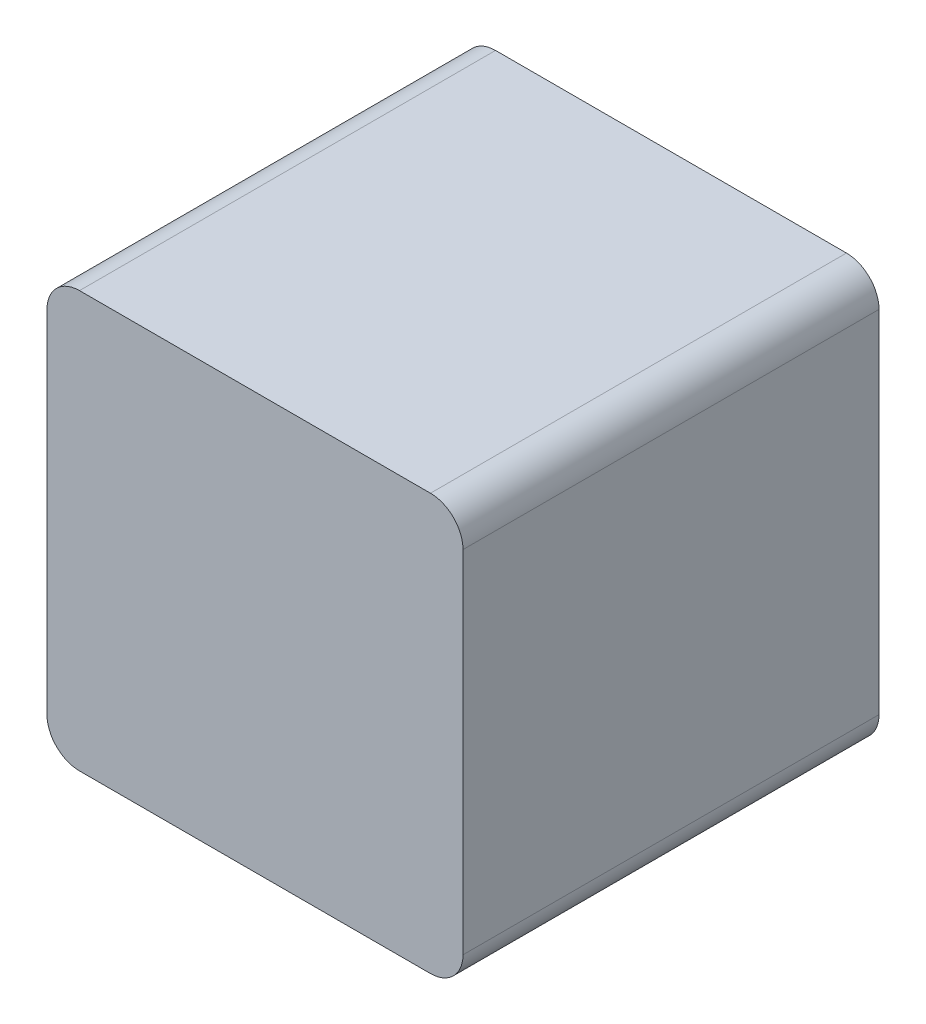
SolidWorks part; units mm, degrees
ref_plane "Front Plane" through (0, 0, 0) normal (0, 0, 1) x (1, 0, 0)
ref_plane "Top Plane" through (0, 0, 0) normal (0, 1, 0) x (1, 0, 0)
ref_plane "Right Plane" through (0, 0, 0) normal (1, 0, 0) x (0, 0, -1)
sketch "Sketch1" plane through (0, 0, 0) normal (0, 0, 1) x (1, 0, 0)
  line L1 (-21.09, -25) -> (21.09, -25)
  line L2 (-25, -21.09) -> (-25, 21.09)
  line L3 (-21.09, 25) -> (21.09, 25)
  line L4 (25, -21.09) -> (25, 21.09)
  line L5 (-25, -25) -> (25, 25) construction
  line L6 (-25, 25) -> (25, -25) construction
  arc A0 (25, -21.09) -> (21.09, -25) centre (21.09, -21.09) cw
  arc A1 (-21.09, -25) -> (-25, -21.09) centre (-21.09, -21.09) cw
  arc A2 (-25, 21.09) -> (-21.09, 25) centre (-21.09, 21.09) cw
  arc A3 (25, 21.09) -> (21.09, 25) centre (21.09, 21.09) ccw
  point P0 (0, 0)
  dimension "D3" = 3.91
  dimension "D1" = 50
  dimension "D2" = 50
extrude "Boss-Extrude1" add sketch "Sketch1" along normal blind 50 contours L4 A3 L3 A2 L2 A1 L1 A0 region at (0, 0, 0)
curve "Curve1"
  spline degree 3 poles (134.3382, 0.0676, 0) (135.0722, -0.0127, 0) (134.3288, 0.1718, 0) (133.4958, 0.389, 0) (130.9679, 0.9485, 0) (127.722, 1.6842, 0) (123.2791, 2.7624, 0) (119.0189, 3.8632, 0) (115.1533, 4.992, 0) (111.9323, 6.0022, 0) (108.5236, 7.152, 0) (104.9433, 8.4273, 0) (101.2019, 9.7787, 0) (97.3212, 11.172, 0) (93.3124, 12.5389, 0) (89.1848, 13.8053, 0) (84.9686, 14.9729, 0) (80.6672, 15.9675, 0) (76.3125, 16.8123, 0) (71.918, 17.4678, 0) (67.5084, 17.9522, 0) (63.0973, 18.2391, 0) (58.7038, 18.3487, 0) (54.3476, 18.2856, 0) (50.0489, 18.0741, 0) (45.8279, 17.7307, 0) (41.6982, 17.2877, 0) (37.681, 16.7137, 0) (33.7895, 16.0466, 0) (30.04, 15.2907, 0) (26.4534, 14.439, 0) (23.0415, 13.5233, 0) (19.8164, 12.5491, 0) (16.8036, 11.4999, 0) (14.0076, 10.4102, 0) (11.4282, 9.3088, 0) (9.0991, 8.1626, 0) (7.0168, 7.015, 0) (5.1888, 5.8855, 0) (3.6644, 4.767, 0) (2.3201, 3.8042, 0) (1.3228, 2.7934, 0) (0.5964, 1.8207, 0) (0.1311, 0.9314, 0) (-0.1111, 0.1721, 0) (0.1695, -0.3855, 0) (0.6378, -0.7482, 0) (1.3518, -1.1672, 0) (2.3905, -1.4533, 0) (3.6631, -1.8176, 0) (5.2215, -2.154, 0) (7.0401, -2.4984, 0) (9.124, -2.7966, 0) (11.4538, -3.0975, 0) (14.0246, -3.3747, 0) (16.8218, -3.6311, 0) (19.8346, -3.8769, 0) (23.0563, -4.0631, 0) (26.4653, -4.2648, 0) (30.053, -4.4028, 0) (33.7993, -4.5422, 0) (37.6899, -4.6211, 0) (41.7064, -4.7007, 0) (45.8333, -4.7204, 0) (50.0534, -4.7392, 0) (54.3501, -4.7026, 0) (58.7037, -4.6488, 0) (63.0935, -4.5403, 0) (67.5007, -4.4291, 0) (71.9072, -4.2633, 0) (76.2977, -4.079, 0) (80.6509, -3.8462, 0) (84.9477, -3.586, 0) (89.1689, -3.3033, 0) (93.2959, -2.9621, 0) (97.3135, -2.5766, 0) (101.2014, -2.1287, 0) (104.9474, -1.6797, 0) (108.5314, -1.2311, 0) (111.9409, -0.8391, 0) (115.1605, -0.5172, 0) (119.0317, -0.1979, 0) (123.2873, 0.0637, 0) (127.7259, 0.184, 0) (130.9739, 0.1815, 0) (133.4832, 0.0405, 0) (134.3382, 0.0676, 0) (135.0722, -0.0127, 0) (134.3288, 0.1718, 0) knots -0.012869 -0.004675 -0.000504 0 0.000523 0.004818 0.013218 0.02567 0.042005 0.061947 0.073246 0.085368 0.098328 0.112007 0.126323 0.141195 0.156438 0.171959 0.187714 0.203571 0.21952 0.235502 0.251436 0.26731 0.28312 0.298782 0.314246 0.329489 0.344412 0.358996 0.37321 0.386953 0.400205 0.412926 0.425016 0.436501 0.447294 0.457349 0.466715 0.475252 0.482966 0.489843 0.495633 0.500739 0.505107 0.508577 0.511777 0.512934 0.51507 0.518046 0.521828 0.526595 0.532338 0.538988 0.546542 0.555016 0.564302 0.574403 0.585285 0.596873 0.609176 0.622083 0.635561 0.649573 0.664015 0.67885 0.694044 0.70949 0.725152 0.740961 0.756808 0.772658 0.788478 0.804161 0.819634 0.834864 0.849749 0.864256 0.878354 0.89192 0.904912 0.917276 0.928899 0.939784 0.959107 0.974989 0.987131 0.995325 0.999496 1 1.000523 1.004818 1.013218 periodic
sketch "Sketch2" plane through (0, 0, 0) normal (0, 0, -1) x (-1, 0, 0)
  spline S0 degree 3 poles (-134.3288, 0.1718) (-135.0722, -0.0127) (-134.3382, 0.0676) (-133.4832, 0.0405) (-130.9739, 0.1815) (-127.7259, 0.184) (-123.2873, 0.0637) (-119.0317, -0.1979) (-115.1605, -0.5172) (-111.9409, -0.8391) (-108.5314, -1.2311) (-104.9474, -1.6797) (-101.2014, -2.1287) (-97.3135, -2.5766) (-93.2959, -2.9621) (-89.1689, -3.3033) (-84.9477, -3.586) (-80.6509, -3.8462) (-76.2977, -4.079) (-71.9072, -4.2633) (-67.5007, -4.4291) (-63.0935, -4.5403) (-58.7037, -4.6488) (-54.3501, -4.7026) (-50.0534, -4.7392) (-45.8333, -4.7204) (-41.7064, -4.7007) (-37.6899, -4.6211) (-33.7993, -4.5422) (-30.053, -4.4028) (-26.4653, -4.2648) (-23.0563, -4.0631) (-19.8346, -3.8769) (-16.8218, -3.6311) (-14.0246, -3.3747) (-11.4538, -3.0975) (-9.124, -2.7966) (-7.0401, -2.4984) (-5.2215, -2.154) (-3.6631, -1.8176) (-2.3905, -1.4533) (-1.3518, -1.1672) (-0.6378, -0.7482) (-0.1695, -0.3855) (0.1111, 0.1721) (-0.1311, 0.9314) (-0.5964, 1.8207) (-1.3228, 2.7934) (-2.3201, 3.8042) (-3.6644, 4.767) (-5.1888, 5.8855) (-7.0168, 7.015) (-9.0991, 8.1626) (-11.4282, 9.3088) (-14.0076, 10.4102) (-16.8036, 11.4999) (-19.8164, 12.5491) (-23.0415, 13.5233) (-26.4534, 14.439) (-30.04, 15.2907) (-33.7895, 16.0466) (-37.681, 16.7137) (-41.6982, 17.2877) (-45.8279, 17.7307) (-50.0489, 18.0741) (-54.3476, 18.2856) (-58.7038, 18.3487) (-63.0973, 18.2391) (-67.5084, 17.9522) (-71.918, 17.4678) (-76.3125, 16.8123) (-80.6672, 15.9675) (-84.9686, 14.9729) (-89.1848, 13.8053) (-93.3124, 12.5389) (-97.3212, 11.172) (-101.2019, 9.7787) (-104.9433, 8.4273) (-108.5236, 7.152) (-111.9323, 6.0022) (-115.1533, 4.992) (-119.0189, 3.8632) (-123.2791, 2.7624) (-127.722, 1.6842) (-130.9679, 0.9485) (-133.4958, 0.389) (-134.3288, 0.1718) (-135.0722, -0.0127) (-134.3382, 0.0676) knots -0.013218 -0.004818 -0.000523 0 0.000504 0.004675 0.012869 0.025011 0.040893 0.060216 0.071101 0.082724 0.095088 0.10808 0.121646 0.135744 0.150251 0.165136 0.180366 0.195839 0.211522 0.227342 0.243192 0.259039 0.274848 0.29051 0.305956 0.32115 0.335985 0.350427 0.364439 0.377917 0.390824 0.403127 0.414715 0.425597 0.435698 0.444984 0.453458 0.461012 0.467662 0.473405 0.478172 0.481954 0.48493 0.487066 0.488223 0.491423 0.494893 0.499261 0.504367 0.510157 0.517034 0.524748 0.533285 0.542651 0.552706 0.563499 0.574984 0.587074 0.599795 0.613047 0.62679 0.641004 0.655588 0.670511 0.685754 0.701218 0.71688 0.73269 0.748564 0.764498 0.78048 0.796429 0.812286 0.828041 0.843562 0.858805 0.873677 0.887993 0.901672 0.914632 0.926754 0.938053 0.957995 0.97433 0.986782 0.995182 0.999477 1 1.000504 1.004675 1.012869 only from (-135, 0) to (-135, 0) construction
  spline S1 degree 3 poles (-134.3288, 0.1718) (-135.0722, -0.0127) (-134.3382, 0.0676) (-133.4832, 0.0405) (-130.9739, 0.1815) (-127.7259, 0.184) (-123.2873, 0.0637) (-119.0317, -0.1979) (-115.1605, -0.5172) (-111.9409, -0.8391) (-108.5314, -1.2311) (-104.9474, -1.6797) (-101.2014, -2.1287) (-97.3135, -2.5766) (-93.2959, -2.9621) (-89.1689, -3.3033) (-84.9477, -3.586) (-80.6509, -3.8462) (-76.2977, -4.079) (-71.9072, -4.2633) (-67.5007, -4.4291) (-63.0935, -4.5403) (-58.7037, -4.6488) (-54.3501, -4.7026) (-50.0534, -4.7392) (-45.8333, -4.7204) (-41.7064, -4.7007) (-37.6899, -4.6211) (-33.7993, -4.5422) (-30.053, -4.4028) (-26.4653, -4.2648) (-23.0563, -4.0631) (-19.8346, -3.8769) (-16.8218, -3.6311) (-14.0246, -3.3747) (-11.4538, -3.0975) (-9.124, -2.7966) (-7.0401, -2.4984) (-5.2215, -2.154) (-3.6631, -1.8176) (-2.3905, -1.4533) (-1.3518, -1.1672) (-0.6378, -0.7482) (-0.1695, -0.3855) (0.1111, 0.1721) (-0.1311, 0.9314) (-0.5964, 1.8207) (-1.3228, 2.7934) (-2.3201, 3.8042) (-3.6644, 4.767) (-5.1888, 5.8855) (-7.0168, 7.015) (-9.0991, 8.1626) (-11.4282, 9.3088) (-14.0076, 10.4102) (-16.8036, 11.4999) (-19.8164, 12.5491) (-23.0415, 13.5233) (-26.4534, 14.439) (-30.04, 15.2907) (-33.7895, 16.0466) (-37.681, 16.7137) (-41.6982, 17.2877) (-45.8279, 17.7307) (-50.0489, 18.0741) (-54.3476, 18.2856) (-58.7038, 18.3487) (-63.0973, 18.2391) (-67.5084, 17.9522) (-71.918, 17.4678) (-76.3125, 16.8123) (-80.6672, 15.9675) (-84.9686, 14.9729) (-89.1848, 13.8053) (-93.3124, 12.5389) (-97.3212, 11.172) (-101.2019, 9.7787) (-104.9433, 8.4273) (-108.5236, 7.152) (-111.9323, 6.0022) (-115.1533, 4.992) (-119.0189, 3.8632) (-123.2791, 2.7624) (-127.722, 1.6842) (-130.9679, 0.9485) (-133.4958, 0.389) (-134.3288, 0.1718) (-135.0722, -0.0127) (-134.3382, 0.0676) knots -0.013218 -0.004818 -0.000523 0 0.000504 0.004675 0.012869 0.025011 0.040893 0.060216 0.071101 0.082724 0.095088 0.10808 0.121646 0.135744 0.150251 0.165136 0.180366 0.195839 0.211522 0.227342 0.243192 0.259039 0.274848 0.29051 0.305956 0.32115 0.335985 0.350427 0.364439 0.377917 0.390824 0.403127 0.414715 0.425597 0.435698 0.444984 0.453458 0.461012 0.467662 0.473405 0.478172 0.481954 0.48493 0.487066 0.488223 0.491423 0.494893 0.499261 0.504367 0.510157 0.517034 0.524748 0.533285 0.542651 0.552706 0.563499 0.574984 0.587074 0.599795 0.613047 0.62679 0.641004 0.655588 0.670511 0.685754 0.701218 0.71688 0.73269 0.748564 0.764498 0.78048 0.796429 0.812286 0.828041 0.843562 0.858805 0.873677 0.887993 0.901672 0.914632 0.926754 0.938053 0.957995 0.97433 0.986782 0.995182 0.999477 1 1.000504 1.004675 1.012869 only from (-135, 0) to (-135, 0)
sketch "Sketch3" plane through (-25, 0, 0) normal (-1, 0, 0) x (0, 0, 1)
  line L0 (15.5, 1.759) -> (15.5, -3.751) construction
  line L1 (50, -21.09) -> (50, 21.09) construction
  line L3 (35.51, 5.382) -> (35.51, -4.888) construction
  line L5 (50, 17.5957) -> (50, 19.5957)
  line L7 (50, 17.5957) -> (50, -7.042)
  line L8 (2, 0) -> (2, -7.0422) construction
  line L9 (137, 0) -> (2, 0) construction
  circle A0 centre (15.5, 1.759) radius 2.06
  circle A1 centre (35.51, 5.382) radius 4.12
  point P0 (50, -7.0424)
  point P3 (138.881, -0.6795)
  point P4 (2, 0)
  point P15 (2, -7.0422)
  point P16 (0, 0)
  point P20 (0, 0)
  point P21 (0, 0)
  point P22 (2.1276, 0)
  point P23 (0, 0)
  point P24 (0, 0)
  point P25 (0, 0)
  point P26 (50, -10.2465)
  dimension "D3" = 4.12
  dimension "D7" = 8.24
  dimension "D1" = 3.4943
  dimension "D2" = 2
  dimension "D4" = 13.5
  dimension "D5" = 5.51
  dimension "D6" = 2
  dimension "D8" = 10.27
  dimension "D9" = 33.51
  dimension "D10" = 135
  dimension "D12" = 2
ref_plane "Plane1" through (-30, 0, 0) normal (-1, 0, 0) x (0, 0, 1)
sketch "Sketch5" plane through (-30, 0, 0) normal (-1, 0, 0) x (0, 0, 1)
  line L1 (50, -5.0357) -> (50, 17.5957)
  line L2 (50, 17.5957) -> (0, 17.5957) construction
  line L3 (0, -21.09) -> (0, 21.09) construction
  circle A0 centre (15.5, 1.759) radius 2.06 construction
  circle A1 centre (35.51, 5.382) radius 4.12 construction
  circle A2 centre (15.5, 1.759) radius 2.06
  circle A3 centre (35.51, 5.382) radius 4.12
  spline S1 degree 3 poles (50, -5.0357) (49.2748, -5.0342) (47.1727, -5.0261) (43.7304, -5.012) (39.7136, -4.9351) (35.8227, -4.8589) (32.0761, -4.722) (28.4881, -4.5864) (25.0788, -4.3871) (21.8567, -4.203) (18.8436, -3.9593) (16.0461, -3.7047) (13.4749, -3.4292) (11.1449, -3.1299) (9.0606, -2.8331) (7.2416, -2.4899) (5.6829, -2.1546) (4.41, -1.7911) (3.3711, -1.5057) (2.6567, -1.0872) (2.1882, -0.7247) (1.9071, -0.1673) (2.1489, 0.5922) (2.6136, 1.4818) (3.3394, 2.4551) (4.3361, 3.4667) (5.6798, 4.4304) (7.2035, 5.55) (9.0309, 6.6808) (11.1125, 7.8299) (13.4409, 8.9778) (16.0197, 10.081) (18.8152, 11.1726) (21.8274, 12.2239) (25.052, 13.2004) (28.4635, 14.1185) (32.0498, 14.9727) (35.7989, 15.7311) (39.6902, 16.4009) (43.7073, 16.9777) (47.1593, 17.3503) (49.2692, 17.5367) (50, 17.5957) knots 1.313335 1.313335 1.313335 1.313335 1.32115 1.335985 1.350427 1.364439 1.377917 1.390824 1.403127 1.414715 1.425597 1.435698 1.444984 1.453458 1.461012 1.467662 1.473405 1.478172 1.481954 1.48493 1.487066 1.488223 1.491423 1.494893 1.499261 1.504367 1.510157 1.517034 1.524748 1.533285 1.542651 1.552706 1.563499 1.574984 1.587074 1.599795 1.613047 1.62679 1.641004 1.655588 1.670511 1.67841 1.67841 1.67841 1.67841
ref_plane "Plane2" through (-30.8375, 1.6161, 0) normal (-0.9986, 0.0523, 0) x (0, 0, -1)
sketch "Sketch8" plane through (-30.8375, 1.6161, 0) normal (-0.9986, 0.0523, 0) x (0, 0, -1)
  line L0 (-137, 1.3084) -> (-2, 1.3084) construction
  line L1 (-137, 1.3084) -> (-2, 1.3084)
  ellipse E0 centre (-35.51, -4.0662) end of major axis (-31.39, -4.0662) minor radius 4.1144 construction
  ellipse E1 centre (-15.5, -0.4482) end of major axis (-13.44, -0.4482) minor radius 2.0572 construction
  ellipse E2 centre (-35.51, -4.0662) end of major axis (-31.39, -4.0662) minor radius 4.1144
  ellipse E3 centre (-15.5, -0.4482) end of major axis (-13.44, -0.4482) minor radius 2.0572
  spline S0 degree 3 poles (-136.3379, 1.2433) (-137.0722, 1.3208) (-136.3282, 1.1393) (-135.4943, 0.9253) (-132.9643, 0.3757) (-129.7156, -0.3475) (-125.2686, -1.4082) (-121.0043, -2.4922) (-117.1344, -3.6056) (-113.9096, -4.6029) (-110.4966, -5.739) (-106.9116, -6.9997) (-103.1651, -8.3359) (-99.2792, -9.7134) (-95.2653, -11.0641) (-91.1329, -12.314) (-86.9123, -13.4649) (-82.6071, -14.4427) (-78.2492, -15.2708) (-73.8522, -15.9097) (-69.4406, -16.3775) (-65.0283, -16.6482) (-60.6342, -16.7419) (-56.278, -16.6632) (-51.9799, -16.4365) (-47.7599, -16.0784) (-43.6316, -15.6212) (-39.6163, -15.0335) (-35.7269, -14.3533) (-31.98, -13.585) (-28.3963, -12.7215) (-24.9875, -11.7948) (-21.7658, -10.8102) (-18.7567, -9.7516) (-15.9644, -8.6533) (-13.3888, -7.5441) (-11.0638, -6.391) (-8.9855, -5.2375) (-7.1615, -4.1029) (-5.641, -2.9804) (-4.3002, -2.0141) (-3.3064, -1.001) (-2.5835, -0.0269) (-2.1214, 0.8628) (-1.8819, 1.622) (-2.1645, 2.1778) (-2.6341, 2.5384) (-3.3497, 2.9542) (-4.3894, 3.2363) (-5.6634, 3.5955) (-7.2231, 3.9259) (-9.0431, 4.2633) (-11.1281, 4.5536) (-13.459, 4.8457) (-16.031, 5.1133) (-18.8292, 5.3593) (-21.8431, 5.5939) (-25.0656, 5.7684) (-28.4755, 5.9575) (-32.0639, 6.0824) (-35.8108, 6.2082) (-39.7019, 6.273) (-43.7189, 6.338) (-47.8461, 6.3429) (-52.0664, 6.3465) (-56.3632, 6.2945) (-60.7169, 6.2251) (-65.1064, 6.1011) (-69.5134, 5.9741) (-73.9196, 5.7928) (-78.3096, 5.5929) (-82.6622, 5.3448) (-86.9582, 5.0695) (-91.1786, 4.772) (-95.3046, 4.4164) (-99.321, 4.017) (-103.2075, 3.5557) (-106.9521, 3.0939) (-110.5346, 2.6329) (-113.9428, 2.2293) (-117.1615, 1.8962) (-121.0317, 1.5634) (-125.2865, 1.2868) (-129.7249, 1.1508) (-132.9731, 1.1416) (-135.483, 1.2734) (-136.3379, 1.2433) (-137.0722, 1.3208) (-136.3282, 1.1393) knots -0.012869 -0.004675 -0.000504 0 0.000523 0.004818 0.013218 0.02567 0.042005 0.061947 0.073246 0.085368 0.098328 0.112007 0.126323 0.141195 0.156438 0.171959 0.187714 0.203571 0.21952 0.235502 0.251436 0.26731 0.28312 0.298782 0.314246 0.329489 0.344412 0.358996 0.37321 0.386953 0.400205 0.412926 0.425016 0.436501 0.447294 0.457349 0.466715 0.475252 0.482966 0.489843 0.495633 0.500739 0.505107 0.508577 0.511777 0.512934 0.51507 0.518046 0.521828 0.526595 0.532338 0.538988 0.546542 0.555016 0.564302 0.574403 0.585285 0.596873 0.609176 0.622083 0.635561 0.649573 0.664015 0.67885 0.694044 0.70949 0.725152 0.740961 0.756808 0.772658 0.788478 0.804161 0.819634 0.834864 0.849749 0.864256 0.878354 0.89192 0.904912 0.917276 0.928899 0.939784 0.959107 0.974989 0.987131 0.995325 0.999496 1 1.000523 1.004818 1.013218 only from (-137, 1.3084) to (-137, 1.3084) construction
  spline S1 degree 3 poles (-136.3379, 1.2433) (-137.0722, 1.3208) (-136.3282, 1.1393) (-135.4943, 0.9253) (-132.9643, 0.3757) (-129.7156, -0.3475) (-125.2686, -1.4082) (-121.0043, -2.4922) (-117.1344, -3.6056) (-113.9096, -4.6029) (-110.4966, -5.739) (-106.9116, -6.9997) (-103.1651, -8.3359) (-99.2792, -9.7134) (-95.2653, -11.0641) (-91.1329, -12.314) (-86.9123, -13.4649) (-82.6071, -14.4427) (-78.2492, -15.2708) (-73.8522, -15.9097) (-69.4406, -16.3775) (-65.0283, -16.6482) (-60.6342, -16.7419) (-56.278, -16.6632) (-51.9799, -16.4365) (-47.7599, -16.0784) (-43.6316, -15.6212) (-39.6163, -15.0335) (-35.7269, -14.3533) (-31.98, -13.585) (-28.3963, -12.7215) (-24.9875, -11.7948) (-21.7658, -10.8102) (-18.7567, -9.7516) (-15.9644, -8.6533) (-13.3888, -7.5441) (-11.0638, -6.391) (-8.9855, -5.2375) (-7.1615, -4.1029) (-5.641, -2.9804) (-4.3002, -2.0141) (-3.3064, -1.001) (-2.5835, -0.0269) (-2.1214, 0.8628) (-1.8819, 1.622) (-2.1645, 2.1778) (-2.6341, 2.5384) (-3.3497, 2.9542) (-4.3894, 3.2363) (-5.6634, 3.5955) (-7.2231, 3.9259) (-9.0431, 4.2633) (-11.1281, 4.5536) (-13.459, 4.8457) (-16.031, 5.1133) (-18.8292, 5.3593) (-21.8431, 5.5939) (-25.0656, 5.7684) (-28.4755, 5.9575) (-32.0639, 6.0824) (-35.8108, 6.2082) (-39.7019, 6.273) (-43.7189, 6.338) (-47.8461, 6.3429) (-52.0664, 6.3465) (-56.3632, 6.2945) (-60.7169, 6.2251) (-65.1064, 6.1011) (-69.5134, 5.9741) (-73.9196, 5.7928) (-78.3096, 5.5929) (-82.6622, 5.3448) (-86.9582, 5.0695) (-91.1786, 4.772) (-95.3046, 4.4164) (-99.321, 4.017) (-103.2075, 3.5557) (-106.9521, 3.0939) (-110.5346, 2.6329) (-113.9428, 2.2293) (-117.1615, 1.8962) (-121.0317, 1.5634) (-125.2865, 1.2868) (-129.7249, 1.1508) (-132.9731, 1.1416) (-135.483, 1.2734) (-136.3379, 1.2433) (-137.0722, 1.3208) (-136.3282, 1.1393) knots -0.012869 -0.004675 -0.000504 0 0.000523 0.004818 0.013218 0.02567 0.042005 0.061947 0.073246 0.085368 0.098328 0.112007 0.126323 0.141195 0.156438 0.171959 0.187714 0.203571 0.21952 0.235502 0.251436 0.26731 0.28312 0.298782 0.314246 0.329489 0.344412 0.358996 0.37321 0.386953 0.400205 0.412926 0.425016 0.436501 0.447294 0.457349 0.466715 0.475252 0.482966 0.489843 0.495633 0.500739 0.505107 0.508577 0.511777 0.512934 0.51507 0.518046 0.521828 0.526595 0.532338 0.538988 0.546542 0.555016 0.564302 0.574403 0.585285 0.596873 0.609176 0.622083 0.635561 0.649573 0.664015 0.67885 0.694044 0.70949 0.725152 0.740961 0.756808 0.772658 0.788478 0.804161 0.819634 0.834864 0.849749 0.864256 0.878354 0.89192 0.904912 0.917276 0.928899 0.939784 0.959107 0.974989 0.987131 0.995325 0.999496 1 1.000523 1.004818 1.013218 only from (-137, 1.3084) to (-137, 1.3084)
ref_plane "Plane3" through (0, 0, 25) normal (0, 0, 1) x (1, 0, 0)
ref_plane "Plane4" through (0, 0, 50) normal (0, 0, 1) x (1, 0, 0)
ref_plane "Plane5" through (0, 0, 75) normal (0, 0, 1) x (1, 0, 0)
ref_plane "Plane6" through (0, 0, 100) normal (0, 0, 1) x (1, 0, 0)
sketch "Sketch10" plane through (0, 0, 25) normal (0, 0, 1) x (1, 0, 0)
  line L4 (-29.9627, 18.3065) -> (-31.1695, -4.7189) construction
  line L5 (-25, 18.0464) -> (-25, -5.0422) construction
  line L6 (-25, 17.5957) -> (-25, 19.5957) construction
  line L7 (-25, 20.0462) -> (-25, -7.0423) construction
  line L8 (-25, 15.187) -> (-25, -6.4673)
  line L10 (-31.1392, -4.1415) -> (-30.221, 13.3797)
  arc A2 (-30.221, 13.3797) -> (-25, 15.187) centre (-32.2669, 27.7346) ccw
  arc A3 (-31.1392, -4.1415) -> (-25, -6.4673) centre (-32.7087, -17.5499) cw
  dimension "D1" = 14.5
  dimension "D2" = 13.5
sketch "Sketch11" plane through (0, 0, 50) normal (0, 0, 1) x (1, 0, 0)
  line L2 (-29.9627, 18.3065) -> (-31.1695, -4.7189) construction
  line L3 (-25, 18.0464) -> (-25, -5.0422) construction
  line L5 (-25, 20.0462) -> (-25, -7.0423) construction
  line L6 (-29.9863, 17.8571) -> (-31.1694, -4.7187)
  line L7 (-25, -7.042) -> (-25, 19.6057)
  arc A0 (-29.9863, 17.8571) -> (-25, 19.6057) centre (-31.8744, 31.2244) ccw
  arc A1 (-31.1694, -4.7187) -> (-25, -7.042) centre (-32.6985, -18.1318) cw
  dimension "D1" = 13.5
  dimension "D2" = 13.5
sketch "Sketch12" plane through (0, 0, 75) normal (0, 0, 1) x (1, 0, 0)
  line L0 (-29.9627, 18.3065) -> (-31.1695, -4.7189) construction
  line L1 (-25, 18.0464) -> (-25, -5.0422) construction
  line L2 (-25, 20.0462) -> (-25, -7.0423) construction
  line L3 (-30.0142, 17.3252) -> (-31.138, -4.1181)
  line L4 (-25, -6.4428) -> (-25, 19.0826)
  arc A0 (-30.0142, 17.3252) -> (-25, 19.0826) centre (-31.8849, 30.695) ccw
  arc A1 (-31.138, -4.1181) -> (-25, -6.4428) centre (-32.7071, -17.5266) cw
  dimension "D1" = 13.5
  dimension "D2" = 13.5
